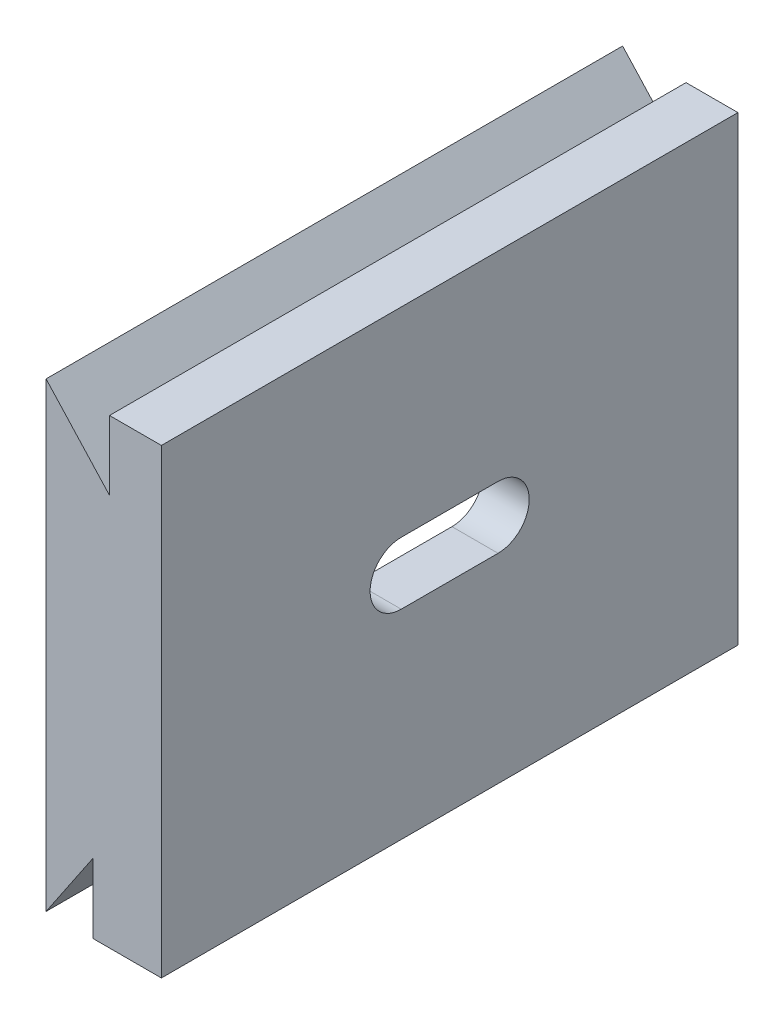
SolidWorks part; units mm, degrees
ref_plane "前视基准面" through (0, 0, 0) normal (0, 0, 1) x (1, 0, 0)
ref_plane "上视基准面" through (0, 0, 0) normal (0, 1, 0) x (1, 0, 0)
ref_plane "右视基准面" through (0, 0, 0) normal (1, 0, 0) x (0, 0, -1)
sketch "草图1" plane through (0, 0, 0) normal (1, 0, 0) x (0, 0, -1)
  line L0 (0, 20) -> (0, -20) construction
  line L1 (-25, 20) -> (25, 20)
  line L2 (-25, 20) -> (-25, -20)
  line L3 (-25, -20) -> (25, -20)
  line L4 (25, 20) -> (25, -20)
  dimension "D1" = 50
  dimension "D2" = 40
extrude "凸台-拉伸1" add sketch "草图1" along normal blind 10
sketch "草图5" plane through (0, 0, -25) normal (0, 0, -1) x (-1, 0, 0)
  line L1 (-5.5, 20) -> (-5.5, 14)
  line L4 (0, 20) -> (-5.5, 20)
  line L5 (-10, 20) -> (0, 20) construction
  line L6 (-5.5, 14) -> (0, 20)
  line L7 (-10, -20) -> (-10, 20) construction
  line L9 (-4.05, -14) -> (0, -20)
  line L10 (0, -20) -> (-4.05, -20)
  line L11 (-4.05, -20) -> (-4.05, -14)
  line M6 (0, 20) -> (-10, 20)
  line M8 (-10, -20) -> (0, -20)
  dimension "D1" = 4.5
  dimension "D2" = 6
extrude "切除-拉伸1" cut sketch "草图5" against normal blind 61 contours L1 L6 M6 | L11 L9 M8 region at (3.6667, 18, -25) region at (2.7, -18, -25)
sketch "草图6" plane through (0, 0, 0) normal (-1, 0, 0) x (0, 0, 1)
  line L0 (-25, 0) -> (-22, 0)
  line L1 (-25, -20) -> (-25, 20) construction
  dimension "D1" = 3
sketch "草图7" plane through (10, 0, 0) normal (1, 0, 0) x (0, 0, -1)
  line L0 (25, 20) -> (-25, 20) construction
  line L1 (-20.5, -13) -> (20.5, -13)
  line L2 (-20.5, -13) -> (-20.5, 13)
  line L3 (-20.5, 13) -> (20.5, 13)
  line L4 (20.5, -13) -> (20.5, 13)
  line L5 (-20.5, -13) -> (20.5, 13) construction
  line L6 (-20.5, 13) -> (20.5, -13) construction
  line L9 (-25, 20) -> (-25, -20) construction
  point P0 (0, 0)
  dimension "D1" = 4.5
  dimension "D2" = 7
extrude "切除-拉伸2" cut sketch "草图7" along normal blind 6 from surface starting at face at (0, 0, 0)
sketch "草图8" plane through (6, 0, 0) normal (-1, 0, 0) x (0, 0, 1)
  line L0 (0, -2.7) -> (0, 2.7) construction
  line L1 (-4.2, 2.7) -> (4.2, 2.7)
  line L2 (-4.2, 2.7) -> (-4.2, -2.7)
  line L3 (-4.2, -2.7) -> (4.2, -2.7)
  line L4 (4.2, 2.7) -> (4.2, -2.7)
  line L5 (-4.2, 2.7) -> (4.2, -2.7) construction
  line L6 (-4.2, -2.7) -> (4.2, 2.7) construction
  circle A0 centre (4.2, 0) radius 2.7
  circle A1 centre (-4.2, 0) radius 2.7
  point P0 (0, 0)
  point P12 (-9.35, 0)
  dimension "D1" = 5.4
  dimension "D2" = 8.4
extrude "切除-拉伸3" cut sketch "草图8" against normal through all contours A1 L2 | A1 L2 | L1 A1 L3 A0 | L4 A0 | L4 A0 region at (6, 0, -3.0541) region at (6, 0, 0) region at (6, 0, -5.3459) region at (6, 0, 5.3459) region at (6, 0, 3.0541)
